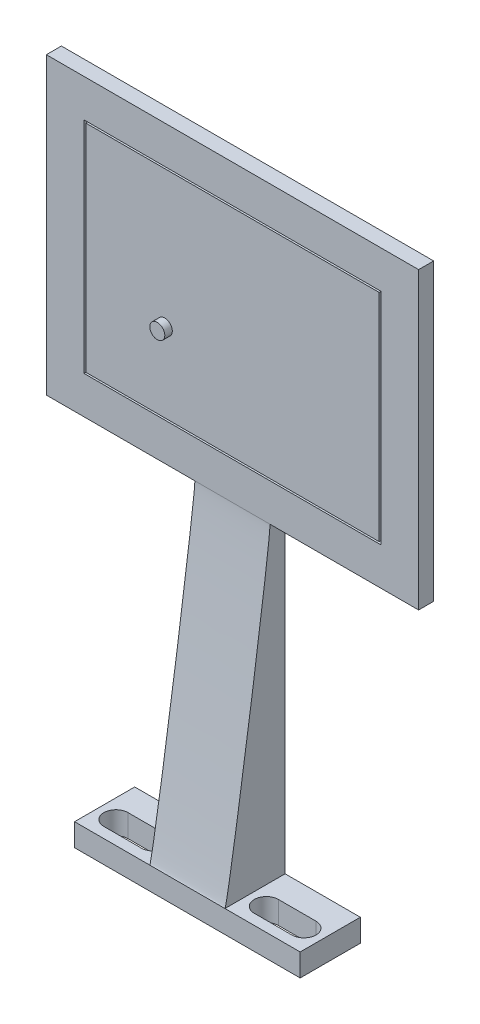
SolidWorks part; units mm, degrees
ref_plane "Front Plane" through (0, 0, 0) normal (0, 0, 1) x (1, 0, 0)
ref_plane "Top Plane" through (0, 0, 0) normal (0, 1, 0) x (1, 0, 0)
ref_plane "Right Plane" through (0, 0, 0) normal (1, 0, 0) x (0, 0, -1)
sketch "Sketch1" plane through (0, 0, 0) normal (0, 0, 1) x (1, 0, 0)
  line L0 (0, -18.2) -> (10.5, -18.2)
  line L1 (0, 0) -> (39, 0)
  line L2 (0, 0) -> (0, -28.7)
  line L3 (0, -28.7) -> (39, -28.7)
  line L4 (39, 0) -> (39, -28.7)
  circle A0 centre (10.5, -18.2) radius 1
  dimension "D5" = 2
  dimension "D1" = 28.7
  dimension "D2" = 39
  dimension "D3" = 10.5
  dimension "D4" = 10.5
extrude "Boss-Extrude2" add sketch "Sketch1" along normal blind 1.5 contours A0 L2 L3 L4 L1 | A0 region at (19.5253, -14.3392, 0)
sketch "Sketch3" plane through (0, 0, 1.5) normal (0, 0, 1) x (1, 0, 0)
  line L0 (0, -18.2) -> (10.5, -18.2) construction
  line L1 (0, -18.2) -> (10.5, -18.2)
  line L4 (39, 0) -> (0, 0)
  line L5 (0, 0) -> (0, -28.7)
  line L6 (0, -28.7) -> (39, -28.7)
  line L7 (39, -28.7) -> (39, 0)
  line L8 (39, 0) -> (0, 0)
  line L9 (0, 0) -> (0, -28.7)
  line L10 (0, -28.7) -> (39, -28.7)
  line L11 (39, -28.7) -> (39, 0)
  line L12 (39, 0) -> (0, 0)
  line L13 (39, -28.7) -> (39, 0)
  line L14 (0, -28.7) -> (39, -28.7)
  line L15 (0, 0) -> (0, -28.7)
  line L16 (39, 0) -> (0, 0)
  line L17 (39, -28.7) -> (39, 0)
  line L18 (0, -28.7) -> (39, -28.7)
  line L19 (0, 0) -> (0, -28.7)
  circle A1 centre (10.5, -18.2) radius 1
  circle A2 centre (10.5, -18.2) radius 1
  dimension "D1" = 0
  dimension "D2" = 0
  dimension "D3" = 0
extrude "Boss-Extrude3" add sketch "Sketch3" along normal blind 1 contours A2 region at (10.5, -17.2283, 1.5)
sketch "Sketch4" plane through (0, 0, 1.5) normal (0, 0, 1) x (1, 0, 0)
  line L1 (0, 0) -> (39, 0)
  line L2 (0, 0) -> (0, -28.7)
  line L3 (0, -28.7) -> (39, -28.7)
  line L4 (39, 0) -> (39, -28.7)
  line L5 (-0.25, 0.25) -> (39.25, 0.25)
  line L6 (-0.25, 0.25) -> (-0.25, -28.95)
  line L7 (-0.25, -28.95) -> (39.25, -28.95)
  line L8 (39.25, 0.25) -> (39.25, -28.95)
  line L9 (-5.25, 5.25) -> (44.25, 5.25)
  line L10 (-5.25, 5.25) -> (-5.25, -33.95)
  line L11 (-5.25, -33.95) -> (44.25, -33.95)
  line L12 (44.25, 5.25) -> (44.25, -33.95)
  dimension "D1" = 0.25
  dimension "D2" = 0.25
  dimension "D3" = 0.25
  dimension "D4" = 0.25
  dimension "D5" = 5
  dimension "D6" = 5
  dimension "D7" = 5
  dimension "D8" = 5
extrude "Boss-Extrude4" add sketch "Sketch4" against normal blind 2 separate body contours L12 L9 L10 L11 L5 L8 L7 L6 region at (19.5, 4.6186, 1.5)
sketch "Sketch6" plane through (0, -33.95, 0) normal (0, -1, 0) x (1, 0, 0)
  line L0 (0, 1.5) -> (39, 1.5) construction
  line L1 (14.5, 1.5) -> (24.5, 1.5)
  line L2 (14.5, 1.5) -> (14.5, -0.5)
  line L3 (14.5, -0.5) -> (24.5, -0.5)
  line L4 (24.5, 1.5) -> (24.5, -0.5)
  line L5 (-5.25, -0.5) -> (44.25, -0.5) construction
  line L6 (14.5, 1.5) -> (-5.25, 1.5) construction
  line L7 (24.5, 1.5) -> (44.25, 1.5) construction
  dimension "D1" = 10
extrude "Boss-Extrude5" add sketch "Sketch6" along normal blind 41.25
sketch "Sketch7" plane through (0, -75.2, 0) normal (0, -1, 0) x (1, 0, 0)
  line L0 (14.5, 1.5) -> (24.5, 1.5)
  line L1 (14.5, -0.5) -> (24.5, -0.5)
  line L5 (-5.25, 1.5) -> (14.5, 1.5) construction
  line L9 (4.5, 7.5) -> (4.5, 1.5)
  line L11 (34.5, 7.5) -> (34.5, 1.5)
  line L12 (24.5, 1.5) -> (44.25, 1.5) construction
  line L13 (34.5, 1.5) -> (24.5, 1.5)
  line L16 (4.5, 1.5) -> (14.5, 1.5)
  line L17 (4.5, 1.5) -> (4.5, -0.5)
  line L18 (4.5, -0.5) -> (14.5, -0.5)
  line L19 (14.5, 1.5) -> (14.5, -0.5)
  line L20 (34.5, 1.5) -> (24.5, 1.5)
  line L21 (34.5, 1.5) -> (34.5, -0.5)
  line L22 (34.5, -0.5) -> (24.5, -0.5)
  line L23 (24.5, 1.5) -> (24.5, -0.5)
  line L25 (4.5, 7.5) -> (4.5, 1.5)
  line L26 (4.5, 1.5) -> (34.5, 1.5)
  line L27 (34.5, 7.5) -> (34.5, 1.5)
  line L31 (14.5, 1.5) -> (14.5, 7.5)
  line L32 (24.5, 1.5) -> (24.5, 7.5)
  line L33 (4.5, 4.5) -> (34.5, 4.5) construction
  line L36 (7, 6.1) -> (12, 6.1)
  line L37 (12, 2.9) -> (7, 2.9)
  line L40 (27, 6.1) -> (32, 6.1)
  line L41 (32, 2.9) -> (27, 2.9)
  line L42 (14.5, 7.5) -> (14.5, 1.5)
  line L43 (4.5, 7.5) -> (14.5, 7.5)
  line L44 (24.5, 1.5) -> (24.5, 7.5)
  line L45 (24.5, 1.5) -> (14.5, 1.5)
  line L46 (14.5, 7.5) -> (24.5, 7.5)
  line L47 (24.5, 7.5) -> (34.5, 7.5)
  arc A11 (27, 6.1) -> (27, 2.9) centre (27, 4.5) ccw
  arc A12 (32, 6.1) -> (32, 2.9) centre (32, 4.5) cw
  arc A15 (7, 6.1) -> (7, 2.9) centre (7, 4.5) ccw
  arc A16 (12, 6.1) -> (12, 2.9) centre (12, 4.5) cw
  line M6 (14.5, 1.5) -> (14.5, -0.5)
  line M7 (14.5, -0.5) -> (24.5, -0.5)
  line M8 (24.5, -0.5) -> (24.5, 1.5)
  line M9 (24.5, 1.5) -> (14.5, 1.5)
  dimension "D5" = 1.6
  dimension "D6" = 5
  dimension "D11" = 2.5
  dimension "D9" = 3.2
  dimension "D12" = 0
  dimension "D3" = 1.6
  dimension "D10" = 3.2
  dimension "D1" = 10
  dimension "D2" = 10
  dimension "D4" = 6
  dimension "D7" = 2.5
  dimension "D8" = 5
extrude "Boss-Extrude10" add sketch "Sketch7" along normal blind 3 contours L9 L33 A15 L36 A16 L42 L43 | L33 L25 L16 L31 A16 L37 A15 | L42 L33 L44 L46 | L33 L31 L32 M9 | L33 L32 L13 L27 A12 L41 A11 | L44 L33 A11 L40 A12 L11 L47 | L22 L21 L13 M8 | M9 M6 M7 M8 | L17 L18 L16 M6 region at (19.5, -75.2, 3) region at (9.5, -75.2, 0.5) region at (19.5, -75.2, 0.5) region at (9.5, -75.2, 2.5049) region at (29.5, -75.2, 2.5049) region at (29.5, -75.2, 0.5) region at (9.5, -75.2, 6.4951) region at (19.5, -75.2, 6) region at (29.5, -75.2, 6.4951)
fillet "Fillet5" radius 41.25 1 edges at (19.5, -75.2, 1.5) second distance 6 conic rho 0.05 first distance on face at (19.5, -34.4625, 1.5)
